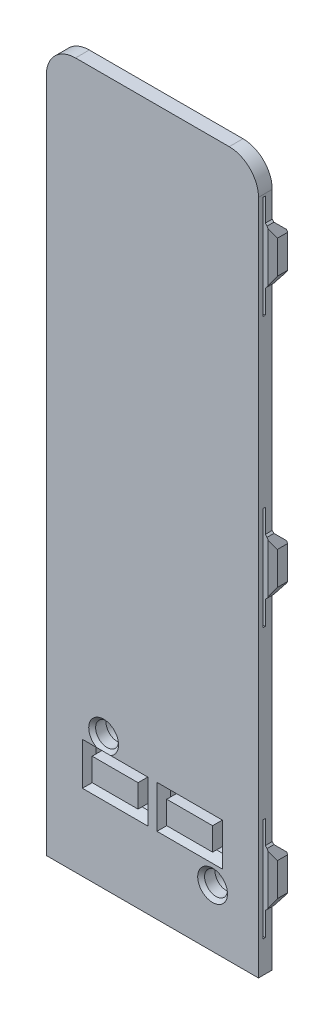
SolidWorks part; units mm, degrees
ref_plane "Ebene vorne" through (0, 0, 0) normal (0, 0, 1) x (1, 0, 0)
ref_plane "Ebene oben" through (0, 0, 0) normal (0, 1, 0) x (1, 0, 0)
ref_plane "Ebene rechts" through (0, 0, 0) normal (1, 0, 0) x (0, 0, -1)
sketch "Skizze2" plane through (0, 0, 4.5) normal (0, 0, 1) x (1, 0, 0)
  line L8 (-63.7575, 39.982) -> (-77.1575, 39.982)
  line L9 (-61.2075, -21.518) -> (-61.2075, 37.432)
  line L10 (-79.7075, -21.518) -> (-61.2075, -21.518)
  line L11 (-79.7075, 37.432) -> (-79.7075, -21.518)
  line L12 (-63.7575, 39.982) -> (-77.1575, 39.982)
  line L13 (-61.2075, -21.518) -> (-61.2075, 37.432)
  line L14 (-79.7075, -21.518) -> (-61.2075, -21.518)
  line L15 (-79.7075, 37.432) -> (-79.7075, -21.518)
  arc A4 (-61.2075, 37.432) -> (-63.7575, 39.982) centre (-63.7575, 37.432) ccw
  arc A5 (-77.1575, 39.982) -> (-79.7075, 37.432) centre (-77.1575, 37.432) ccw
  arc A6 (-61.2075, 37.432) -> (-63.7575, 39.982) centre (-63.7575, 37.432) ccw
  arc A7 (-77.1575, 39.982) -> (-79.7075, 37.432) centre (-77.1575, 37.432) ccw
  dimension "D1" = 0.25
extrude "Aufsatz-Linear austragen1" add sketch "Skizze2" against normal blind 1.2
sketch "Skizze3" plane through (0, 0, 3.3) normal (0, 0, -1) x (-1, 0, 0)
  line L0 (70.4575, 41.3791) -> (70.4575, 26.8483) construction
  line L1 (70.4575, 9.232) -> (70.4575, 42.3392) construction
  line L3 (62.4075, 37.232) -> (63.6075, 37.232)
  line L4 (62.4075, 37.232) -> (62.4075, 28.232)
  line L5 (62.4075, 28.232) -> (63.6075, 28.232)
  line L6 (63.6075, 37.232) -> (63.6075, 28.232)
  line L7 (60.3575, 32.732) -> (65.9583, 32.732) construction
  line L8 (60.3575, 31.232) -> (60.3575, 34.232) construction
  line L9 (62.4075, 13.732) -> (63.6075, 13.732)
  line L10 (62.4075, 13.732) -> (62.4075, 4.732)
  line L11 (62.4075, 4.732) -> (63.6075, 4.732)
  line L12 (63.6075, 13.732) -> (63.6075, 4.732)
  line L13 (60.3575, 9.232) -> (65.9583, 9.232) construction
  line L14 (62.4075, -9.768) -> (63.6075, -9.768)
  line L15 (62.4075, -9.768) -> (62.4075, -18.768)
  line L16 (62.4075, -18.768) -> (63.6075, -18.768)
  line L17 (63.6075, -9.768) -> (63.6075, -18.768)
  line L18 (60.3575, -14.268) -> (65.9583, -14.268) construction
  line L19 (60.3575, -15.768) -> (60.3575, -12.768) construction
  line L20 (80.5575, -14.268) -> (74.9568, -14.268) construction
  line L21 (80.5575, 9.232) -> (74.9568, 9.232) construction
  line L22 (80.5575, 32.732) -> (74.9568, 32.732) construction
  line L23 (77.3075, -9.768) -> (77.3075, -18.768)
  line L24 (78.5075, -18.768) -> (77.3075, -18.768)
  line L25 (78.5075, -9.768) -> (78.5075, -18.768)
  line L26 (78.5075, -9.768) -> (77.3075, -9.768)
  line L27 (77.3075, 13.732) -> (77.3075, 4.732)
  line L28 (78.5075, 4.732) -> (77.3075, 4.732)
  line L29 (78.5075, 13.732) -> (78.5075, 4.732)
  line L30 (78.5075, 13.732) -> (77.3075, 13.732)
  line L31 (77.3075, 37.232) -> (77.3075, 28.232)
  line L32 (78.5075, 28.232) -> (77.3075, 28.232)
  line L33 (78.5075, 37.232) -> (78.5075, 28.232)
  line L34 (78.5075, 37.232) -> (77.3075, 37.232)
  line L35 (61.2075, -21.518) -> (61.2075, 37.432) construction
  dimension "D1" = 2
  dimension "D2" = 2
  dimension "D3" = 1.2
  dimension "D5" = 1.2
  dimension "D4" = 3
extrude "Schnitt-Linear austragen1" cut sketch "Skizze3" against normal offset from surface (0.8 mm away) 0.4 up to face at (-70.4575, 18.808, 4.5)
sketch "Skizze4" plane through (-61.2075, 0, 0) normal (1, 0, 0) x (0, 0, -1)
  line L0 (-2.5, 32.732) -> (-6.7084, 32.732) construction
  line L1 (-2.5, 31.232) -> (-2.5, 34.232) construction
  line L2 (-4.5, -21.518) -> (-4.5, 37.432) construction
  line L3 (-4.1, 37.232) -> (-3.9, 37.232)
  line L4 (-4.1, 37.232) -> (-4.1, 28.232)
  line L5 (-4.1, 28.232) -> (-3.9, 28.232)
  line L6 (-3.9, 37.232) -> (-3.9, 28.232)
  line L7 (-4, 35.232) -> (-2.5, 35.232) construction
  line L8 (-4, 30.232) -> (-2.5, 30.232) construction
  line L9 (-4.1, 13.732) -> (-3.9, 13.732)
  line L10 (-4.1, 13.732) -> (-4.1, 4.732)
  line L11 (-4.1, 4.732) -> (-3.9, 4.732)
  line L12 (-3.9, 13.732) -> (-3.9, 4.732)
  line L13 (-2.5, 9.232) -> (-6.7084, 9.232) construction
  line L14 (-4.1, -9.768) -> (-3.9, -9.768)
  line L15 (-4.1, -9.768) -> (-4.1, -18.768)
  line L16 (-4.1, -18.768) -> (-3.9, -18.768)
  line L17 (-3.9, -9.768) -> (-3.9, -18.768)
  line L18 (-2.5, -14.268) -> (-6.7084, -14.268) construction
  line L19 (-2.5, -15.768) -> (-2.5, -12.768) construction
  dimension "D1" = 0.4
  dimension "D2" = 0.2
  dimension "D3" = 2
  dimension "D4" = 2
extrude "Schnitt-Linear austragen2" cut sketch "Skizze4" against normal up to next
ref_plane "Ebene1" through (-70.4575, 0, 0) normal (-1, 0, 0) x (0, 0, 1)
mirror "Spiegeln1" about plane through (-70.4575, 0, 0) normal (-1, 0, 0) of "Schnitt-Linear austragen2"
sketch "Skizze5" plane through (0, 0, 3.3) normal (0, 0, -1) x (-1, 0, 0)
  line L0 (62.4075, 37.232) -> (62.4075, 28.232) construction
  line L1 (60.5575, 35.032) -> (62.4075, 35.032)
  line L2 (60.5575, 35.032) -> (60.5575, 30.432)
  line L3 (60.5575, 30.432) -> (62.4075, 30.432)
  line L4 (62.4075, 35.032) -> (62.4075, 30.432)
  line L5 (60.3575, 32.732) -> (64.8062, 32.732) construction
  line L6 (60.3575, 31.232) -> (60.3575, 34.232) construction
  line L7 (70.4575, 31.332) -> (70.4575, 43.9736) construction
  line L8 (60.5575, 11.532) -> (62.4075, 11.532)
  line L9 (60.5575, 11.532) -> (60.5575, 6.932)
  line L10 (60.5575, 6.932) -> (62.4075, 6.932)
  line L11 (62.4075, 11.532) -> (62.4075, 6.932)
  line L12 (60.3575, 9.232) -> (64.8062, 9.232) construction
  line L13 (60.5575, -11.968) -> (62.4075, -11.968)
  line L14 (60.5575, -11.968) -> (60.5575, -16.568)
  line L15 (60.5575, -16.568) -> (62.4075, -16.568)
  line L16 (62.4075, -11.968) -> (62.4075, -16.568)
  line L17 (60.3575, -14.268) -> (64.8062, -14.268) construction
  line L18 (60.3575, -15.768) -> (60.3575, -12.768) construction
  line L19 (80.5575, -14.268) -> (76.1089, -14.268) construction
  line L20 (80.5575, 9.232) -> (76.1089, 9.232) construction
  line L21 (80.5575, 32.732) -> (76.1089, 32.732) construction
  line L22 (78.5075, -11.968) -> (78.5075, -16.568)
  line L23 (80.3575, -16.568) -> (78.5075, -16.568)
  line L24 (80.3575, -11.968) -> (80.3575, -16.568)
  line L25 (80.3575, -11.968) -> (78.5075, -11.968)
  line L26 (78.5075, 11.532) -> (78.5075, 6.932)
  line L27 (80.3575, 6.932) -> (78.5075, 6.932)
  line L28 (80.3575, 11.532) -> (80.3575, 6.932)
  line L29 (80.3575, 11.532) -> (78.5075, 11.532)
  line L30 (78.5075, 35.032) -> (78.5075, 30.432)
  line L31 (80.3575, 30.432) -> (78.5075, 30.432)
  line L32 (80.3575, 35.032) -> (80.3575, 30.432)
  line L33 (80.3575, 35.032) -> (78.5075, 35.032)
  dimension "D1" = 0.2
  dimension "D2" = 0.2
  dimension "D3" = 0.2
extrude "Aufsatz-Linear austragen2" add sketch "Skizze5" along normal blind 0.7 and the other way blind 0.6
chamfer "Fase3" distance 0.4 angle 45 6 edges at (-80.3575, -14.268, 3.9) (-80.3575, 9.232, 3.9) (-80.3575, 32.732, 3.9) (-60.5575, -14.268, 3.9) (-60.5575, 9.232, 3.9) (-60.5575, 32.732, 3.9)
chamfer "Fase1" distance 0.5 angle 60 12 edges at (-60.5575, -11.968, 3.05) (-80.3575, -16.568, 3.05) (-80.3575, 6.932, 3.05) (-60.5575, 11.532, 3.05) (-60.5575, -16.568, 3.05) (-80.3575, -11.968, 3.05) (-60.5575, 6.932, 3.05) (-80.3575, 11.532, 3.05) (-80.3575, 35.032, 3.05) (-80.3575, 30.432, 3.05) (-60.5575, 30.432, 3.05) (-60.5575, 35.032, 3.05)
chamfer "Fase4" distance 0.7 angle 45 18 edges at (-79.1825, -16.568, 2.6) (-78.5075, -14.268, 2.6) (-79.1825, -11.968, 2.6) (-61.7325, -16.568, 2.6) (-62.4075, -14.268, 2.6) (-61.7325, -11.968, 2.6) (-61.7325, 6.932, 2.6) (-62.4075, 9.232, 2.6) (-61.7325, 11.532, 2.6) (-79.1825, 11.532, 2.6) (-78.5075, 9.232, 2.6) (-79.1825, 6.932, 2.6) (-79.1825, 35.032, 2.6) (-78.5075, 32.732, 2.6) (-79.1825, 30.432, 2.6) (-61.7325, 35.032, 2.6) (-62.4075, 32.732, 2.6) (-61.7325, 30.432, 2.6)
chamfer "Fase5" distance 0.15 angle 45 12 edges at (-79.7075, 35.032, 3.6) (-79.7075, 30.432, 3.6) (-79.7075, 6.932, 3.6) (-79.7075, 11.532, 3.6) (-79.7075, -11.968, 3.6) (-79.7075, -16.568, 3.6) (-61.2075, -16.568, 3.6) (-61.2075, -11.968, 3.6) (-61.2075, 11.532, 3.6) (-61.2075, 6.932, 3.6) (-61.2075, 30.432, 3.6) (-61.2075, 35.032, 3.6)
sketch "Skizze6" plane through (0, 0, 4.5) normal (0, 0, 1) x (1, 0, 0)
  line L0 (-61.2075, -21.518) -> (-61.2075, 37.432) construction
  line L1 (-79.7075, -21.518) -> (-61.2075, -21.518) construction
  line L2 (-79.7075, 37.432) -> (-79.7075, -21.518) construction
  circle A0 centre (-65.2075, -16.518) radius 1
  circle A1 centre (-74.7075, -10.018) radius 1
  dimension "D3" = 2
  dimension "D6" = 2
  dimension "D1" = 4
  dimension "D2" = 5
  dimension "D4" = 5
  dimension "D5" = 11.5
extrude "Schnitt-Linear austragen3" cut sketch "Skizze6" against normal through all
sketch "Skizze7" plane through (0, 0, 3.3) normal (0, 0, -1) x (-1, 0, 0)
  line L0 (70.4575, -21.518) -> (70.4575, 3.6801) construction
  line L1 (79.7075, -21.518) -> (61.2075, -21.518) construction
  line L2 (70.4575, -4.4) -> (70.4575, 4.4) construction
  line L3 (79.7075, 6.782) -> (79.7075, -11.818) construction
  line L4 (71.7075, -12.018) -> (75.7075, -12.018)
  line L5 (71.7075, -12.018) -> (71.7075, -14.018)
  line L6 (71.7075, -14.018) -> (75.7075, -14.018)
  line L7 (75.7075, -12.018) -> (75.7075, -14.018)
  line L8 (71.7075, -12.018) -> (75.7075, -14.018) construction
  line L9 (71.7075, -14.018) -> (75.7075, -12.018) construction
  line L10 (69.2075, -14.018) -> (65.2075, -12.018) construction
  line L11 (69.2075, -12.018) -> (65.2075, -14.018) construction
  line L12 (65.2075, -12.018) -> (65.2075, -14.018)
  line L13 (69.2075, -14.018) -> (65.2075, -14.018)
  line L14 (69.2075, -12.018) -> (69.2075, -14.018)
  line L15 (69.2075, -12.018) -> (65.2075, -12.018)
  point P6 (73.7075, -13.018)
  point P17 (67.2075, -13.018)
  dimension "D1" = 6
  dimension "D2" = 8.5
  dimension "D3" = 2
  dimension "D4" = 4
extrude "Aufsatz-Linear austragen3" add sketch "Skizze7" along normal blind 2.8
sketch "Skizze8" plane through (0, 0, 3.3) normal (0, 0, -1) x (-1, 0, 0)
  line L0 (75.7075, -14.018) -> (75.7075, -12.018) construction
  line L1 (75.7075, -12.018) -> (71.7075, -12.018) construction
  line L2 (71.7075, -12.018) -> (71.7075, -14.018) construction
  line L3 (71.7075, -14.018) -> (75.7075, -14.018) construction
  line L4 (69.2075, -14.018) -> (69.2075, -12.018) construction
  line L5 (69.2075, -12.018) -> (65.2075, -12.018) construction
  line L6 (65.2075, -12.018) -> (65.2075, -14.018) construction
  line L7 (65.2075, -14.018) -> (69.2075, -14.018) construction
  line L8 (75.7075, -14.018) -> (75.7075, -12.018)
  line L9 (75.7075, -12.018) -> (71.7075, -12.018)
  line L10 (71.7075, -12.018) -> (71.7075, -14.018)
  line L11 (71.7075, -14.018) -> (75.7075, -14.018)
  line L12 (69.2075, -14.018) -> (69.2075, -12.018)
  line L13 (69.2075, -12.018) -> (65.2075, -12.018)
  line L14 (65.2075, -12.018) -> (65.2075, -14.018)
  line L15 (65.2075, -14.018) -> (69.2075, -14.018)
  line L28 (69.4575, -14.268) -> (69.4575, -11.768)
  line L29 (69.4575, -11.768) -> (64.9575, -11.768)
  line L30 (64.9575, -11.768) -> (64.9575, -14.268)
  line L31 (64.9575, -14.268) -> (69.4575, -14.268)
  line L32 (69.4575, -14.268) -> (69.4575, -11.768)
  line L33 (69.4575, -11.768) -> (64.9575, -11.768)
  line L34 (64.9575, -11.768) -> (64.9575, -14.268)
  line L35 (64.9575, -14.268) -> (69.4575, -14.268)
  line L40 (75.9575, -14.268) -> (75.9575, -11.768)
  line L41 (75.9575, -11.768) -> (71.4575, -11.768)
  line L42 (71.4575, -11.768) -> (71.4575, -14.268)
  line L43 (71.4575, -14.268) -> (75.9575, -14.268)
  line L44 (75.9575, -14.268) -> (75.9575, -11.768)
  line L45 (75.9575, -11.768) -> (71.4575, -11.768)
  line L46 (71.4575, -11.768) -> (71.4575, -14.268)
  line L47 (71.4575, -14.268) -> (75.9575, -14.268)
  dimension "D1" = 0.25
  dimension "D2" = 0.25
extrude "Schnitt-Linear austragen4" cut sketch "Skizze8" against normal through all
sketch "Skizze9" plane through (0, 0, 3.3) normal (0, 0, -1) x (-1, 0, 0)
  line L72 (76.2075, -14.518) -> (76.2075, -11.518)
  line L73 (71.2075, -14.518) -> (76.2075, -14.518)
  line L74 (71.2075, -11.518) -> (71.2075, -14.518)
  line L75 (76.2075, -11.518) -> (71.2075, -11.518)
  line L76 (76.2075, -14.518) -> (76.2075, -11.518) construction
  line L77 (71.2075, -14.518) -> (76.2075, -14.518) construction
  line L78 (71.2075, -11.518) -> (71.2075, -14.518) construction
  line L79 (76.2075, -11.518) -> (71.2075, -11.518) construction
  line L90 (64.7075, -11.518) -> (64.7075, -14.518)
  line L91 (64.7075, -14.518) -> (69.7075, -14.518)
  line L92 (69.7075, -14.518) -> (69.7075, -11.518)
  line L93 (69.7075, -11.518) -> (64.7075, -11.518)
  line L94 (64.7075, -11.518) -> (64.7075, -14.518) construction
  line L95 (64.7075, -14.518) -> (69.7075, -14.518) construction
  line L96 (69.7075, -14.518) -> (69.7075, -11.518) construction
  line L97 (69.7075, -11.518) -> (64.7075, -11.518) construction
  dimension "D1" = 0.25
  dimension "D2" = 0.25
ref_plane "Ebene3" through (0, -13.018, 0) normal (0, -1, 0) x (-1, 0, 0)
sketch "Skizze16" plane through (0, 0, 3.3) normal (0, 0, -1) x (-1, 0, 0)
  circle A4 centre (65.2075, -16.518) radius 1.5
  circle A5 centre (74.7075, -10.018) radius 1.5
  circle A6 centre (74.7075, -10.018) radius 1.125
  circle A7 centre (65.2075, -16.518) radius 1.125
  dimension "D1" = 3
  dimension "D2" = 2.25
extrude "Aufsatz-Linear austragen8" add sketch "Skizze16" along normal blind 2
ref_plane "Ebene4" through (0, 0, 2.8) normal (0, 0, -1) x (-1, 0, 0)
sketch "Skizze17" plane through (0, 0, 2.8) normal (0, 0, -1) x (-1, 0, 0)
  line L0 (71.7075, -12.018) -> (71.7075, -7.018)
  line L8 (71.7075, -7.018) -> (72.6075, -7.018)
  line L9 (72.6075, -7.018) -> (72.6075, -12.018)
  line L10 (75.7075, -12.018) -> (71.7075, -12.018) construction
  line L20 (72.6075, -12.018) -> (71.7075, -12.018)
  line L22 (75.7075, -14.018) -> (75.7075, -19.018)
  line L23 (75.7075, -19.018) -> (74.8075, -19.018)
  line L25 (74.8075, -19.018) -> (74.8075, -14.018)
  line L26 (71.7075, -14.018) -> (75.7075, -14.018) construction
  line L27 (74.8075, -14.018) -> (75.7075, -14.018)
  line L28 (65.2075, -12.018) -> (65.2075, -7.018)
  line L29 (65.2075, -7.018) -> (66.1075, -7.018)
  line L30 (66.1075, -7.018) -> (66.1075, -12.018)
  line L31 (69.2075, -12.018) -> (65.2075, -12.018) construction
  line L32 (66.1075, -12.018) -> (65.2075, -12.018)
  line L33 (69.2075, -14.018) -> (69.2075, -19.018)
  line L34 (69.2075, -19.018) -> (68.3075, -19.018)
  line L35 (68.3075, -19.018) -> (68.3075, -14.018)
  line L36 (65.2075, -14.018) -> (69.2075, -14.018) construction
  line L37 (68.3075, -14.018) -> (69.2075, -14.018)
  dimension "D1" = 0.9
  dimension "D2" = 5
extrude "Aufsatz-Linear austragen9" add sketch "Skizze17" along normal blind 0.3
sketch "Skizze18" plane through (0, 0, 3.3) normal (0, 0, -1) x (-1, 0, 0)
  line L0 (65.2075, -7.018) -> (65.2075, -12.018) construction
  line L1 (65.2075, -7.018) -> (66.1075, -7.018)
  line L2 (65.2075, -7.018) -> (65.2075, -8.018)
  line L3 (65.2075, -8.018) -> (66.1075, -8.018)
  line L4 (66.1075, -7.018) -> (66.1075, -8.018)
  line L5 (66.1075, -7.018) -> (65.2075, -7.018) construction
  line L6 (66.1075, -12.018) -> (66.1075, -7.018) construction
  line L7 (72.6075, -12.018) -> (72.6075, -7.018) construction
  line L8 (71.7075, -7.018) -> (72.6075, -7.018)
  line L9 (71.7075, -7.018) -> (71.7075, -8.018)
  line L10 (71.7075, -8.018) -> (72.6075, -8.018)
  line L11 (72.6075, -7.018) -> (72.6075, -8.018)
  line L12 (74.8075, -14.018) -> (74.8075, -19.018) construction
  line L13 (68.3075, -19.018) -> (69.2075, -19.018)
  line L14 (68.3075, -19.018) -> (68.3075, -18.018)
  line L15 (68.3075, -18.018) -> (69.2075, -18.018)
  line L16 (69.2075, -19.018) -> (69.2075, -18.018)
  line L17 (74.8075, -19.018) -> (75.7075, -19.018)
  line L18 (74.8075, -19.018) -> (74.8075, -18.018)
  line L19 (74.8075, -18.018) -> (75.7075, -18.018)
  line L20 (75.7075, -19.018) -> (75.7075, -18.018)
  line L21 (75.7075, -19.018) -> (75.7075, -14.018) construction
  line L22 (74.8075, -19.018) -> (75.7075, -19.018) construction
  point P30 (74.8075, -19.0266)
  point P31 (75.7075, -19.018)
  point P34 (69.2075, -19.018)
  dimension "D1" = 1
extrude "Aufsatz-Linear austragen10" add sketch "Skizze18" along normal up to next
chamfer "Fase6" distance 0.5 angle 45 16 edges at (-66.1075, -7.518, 3.3) (-65.6575, -7.018, 3.3) (-65.2075, -7.518, 3.3) (-65.6575, -8.018, 3.3) (-72.6075, -7.518, 3.3) (-72.1575, -7.018, 3.3) (-71.7075, -7.518, 3.3) (-72.1575, -8.018, 3.3) (-75.7075, -18.518, 3.3) (-75.2575, -18.018, 3.3) (-74.8075, -18.518, 3.3) (-75.2575, -19.018, 3.3) (-69.2075, -18.518, 3.3) (-68.7575, -18.018, 3.3) (-68.3075, -18.518, 3.3) (-68.7575, -19.018, 3.3)
chamfer "Fase7" distance 0.3 angle 45 4 edges at (-65.6575, -7.018, 2.5) (-72.1575, -7.018, 2.5) (-75.2575, -19.018, 2.5) (-68.7575, -19.018, 2.5)
chamfer "Fase8" distance 0.3 angle 45 4 edges at (-75.8325, -10.018, 1.3) (-64.2075, -16.518, 4.5) (-73.7075, -10.018, 4.5) (-66.3325, -16.518, 1.3)
chamfer "Fase9" distance 0.6 angle 45 8 edges at (-71.4575, -13.018, 4.5) (-73.7075, -11.768, 4.5) (-75.9575, -13.018, 4.5) (-73.7075, -14.268, 4.5) (-64.9575, -13.018, 4.5) (-67.2075, -11.768, 4.5) (-69.4575, -13.018, 4.5) (-67.2075, -14.268, 4.5)
equation "\"6ß\"=50"
